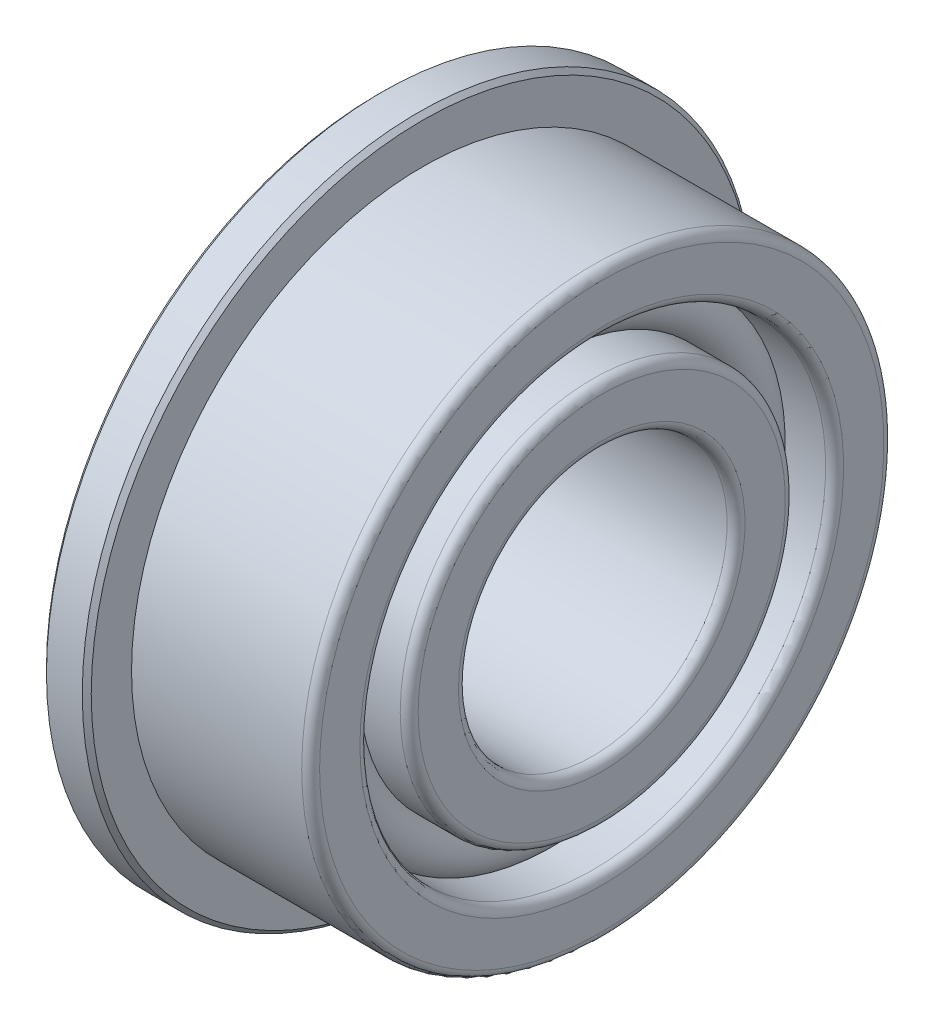
SolidWorks part; units mm, degrees
material "1Cr18Ni9Ti"
ref_plane "前视" through (0, 0, 0) normal (0, 0, 1) x (1, 0, 0)
ref_plane "上视" through (0, 0, 0) normal (0, 1, 0) x (1, 0, 0)
ref_plane "右视" through (0, 0, 0) normal (1, 0, 0) x (0, 0, -1)
sketch "草图1" plane through (0, 0, 0) normal (0, 0, 1) x (1, 0, 0)
  line L0 (0, 0) -> (5.81, 0) construction
  line L1 (2.5, 3.3596) -> (2.5, 6.1404) construction
  line L2 (0, 6.5) -> (3.8, 6.5)
  line L3 (0, 6.5) -> (0, 5.3916)
  line L4 (0.1916, 5.2) -> (2.1031, 5.2)
  line L5 (4, 6.3) -> (4, 5.4)
  line L6 (0, 3) -> (3.8, 3)
  line L7 (0, 3) -> (0, 4.1084)
  line L8 (0.1916, 4.3) -> (2.1031, 4.3)
  line L9 (4, 3.2) -> (4, 4.1)
  line L10 (2.8969, 5.2) -> (3.8, 5.2)
  line L11 (2.8969, 4.3) -> (3.8, 4.3)
  arc A0 (2.1031, 5.2) -> (2.1031, 4.3) centre (2.5, 4.75) ccw
  arc A1 (2.8969, 4.3) -> (2.8969, 5.2) centre (2.5, 4.75) ccw
  arc A3 (3.8, 6.5) -> (4, 6.3) centre (3.8, 6.3) cw
  arc A4 (3.8, 5.2) -> (4, 5.4) centre (3.8, 5.4) ccw
  arc A5 (3.8, 4.3) -> (4, 4.1) centre (3.8, 4.1) cw
  arc A6 (3.8, 3) -> (4, 3.2) centre (3.8, 3.2) ccw
  arc A8 (0, 4.1084) -> (0.1916, 4.3) centre (0.1916, 4.1084) cw
  arc A9 (0, 5.3916) -> (0.1916, 5.2) centre (0.1916, 5.3916) ccw
  point P23 (4, 6.5)
  point P30 (4, 3)
  point P36 (0, 4.3)
  point P39 (0, 5.2)
  dimension "D4" = 1.2
  dimension "D2" = 6
  dimension "D5" = 4
  dimension "D6" = 13
  dimension "D7" = 1.75
  dimension "D10" = 1.5
revolve "旋转1" add sketch "草图1" angle 360 about L0
sketch "草图2" plane through (0, 0, 0) normal (-1, 0, 0) x (0, 0, 1)
  circle A0 centre (0, 0) radius 7.5
  circle A1 centre (0, 0) radius 3
  dimension "D1" = 15
  dimension "D2" = 6
extrude "拉伸1" add sketch "草图2" along normal blind 1
chamfer "倒角1" distance 0.1 angle 45 3 edges at (0, 0, 7.5) (-1, 0, 7.5) (-1, 0, 3)
